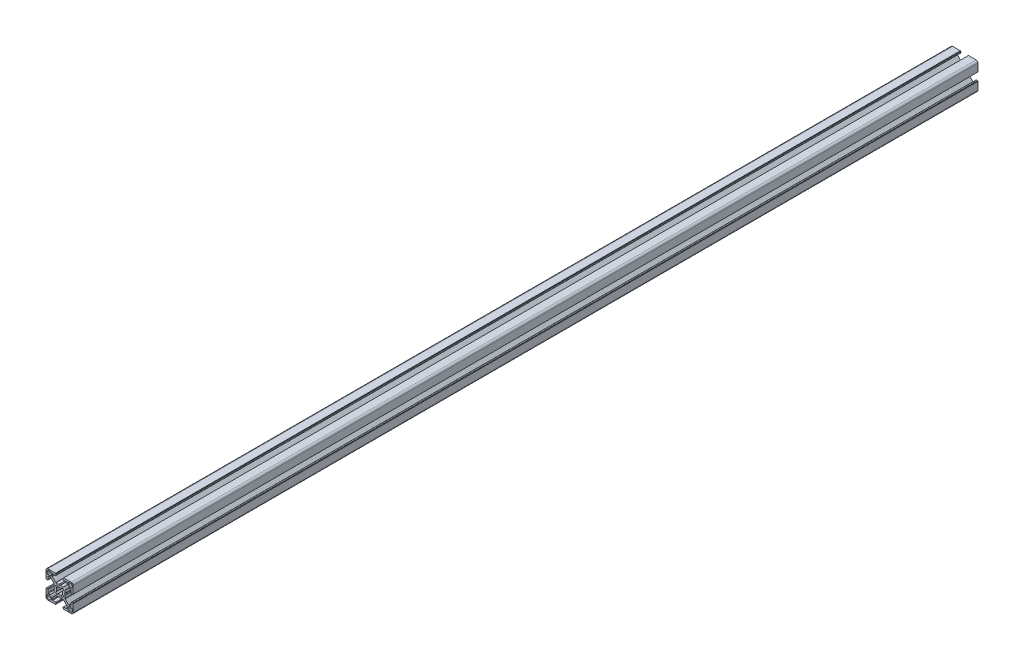
SolidWorks part; units mm, degrees
ref_plane "Front Plane" through (0, 0, 0) normal (0, 0, 1) x (1, 0, 0)
ref_plane "Top Plane" through (0, 0, 0) normal (0, 1, 0) x (1, 0, 0)
ref_plane "Right Plane" through (0, 0, 0) normal (1, 0, 0) x (0, 0, -1)
sketch "Sketch1" plane through (0, 0, 0) normal (0, 0, 1) x (1, 0, 0)
  line L0 (-15, 0) -> (15, 0) construction
  line L1 (0, -15) -> (0, 15) construction
  line L2 (-4.5, 15) -> (4.5, 15) construction
  line L3 (-4, -15) -> (4, -15) construction
  line L4 (-4.5, 15) -> (-4.5, 14.5)
  line L5 (-4.5, 14.5) -> (-4, 14.5)
  line L6 (-4, 14.5) -> (-4, 13.29)
  line L7 (-4.5, 12.79) -> (-7.7675, 12.79)
  line L8 (-8.2675, 12.29) -> (-8.2675, 10.2707)
  line L9 (-8.1211, 9.9171) -> (-4.3504, 6.1464)
  line L10 (-3.9968, 6) -> (0, 6)
  line L11 (0, 0) -> (-15, 15) construction
  line L12 (-4.5, 15) -> (-12.968, 15)
  line L14 (-12.705, 9.5135) -> (-10.5135, 9.5135)
  line L15 (-13.705, 10.5135) -> (-13.705, 12.705)
  line L16 (-12.705, 13.705) -> (-10.5135, 13.705)
  line L17 (-9.5135, 10.5135) -> (-9.5135, 12.705)
  line L18 (-13.705, 9.5135) -> (-9.5135, 13.705) construction
  line L19 (-13.705, 13.705) -> (-9.5135, 9.5135) construction
  line L20 (-3.1568, 4.5038) -> (-1.5303, 3.1477) construction
  line L21 (-4.5038, 3.1568) -> (-3.1477, 1.5303) construction
  line L22 (-6, 3.9968) -> (-6, 0)
  line L23 (-9.9171, 8.1211) -> (-6.1464, 4.3504)
  line L24 (-15, 4.5) -> (-15, 12.968)
  line L25 (-12.29, 8.2675) -> (-10.2707, 8.2675)
  line L26 (-12.79, 4.5) -> (-12.79, 7.7675)
  line L27 (-14.5, 4) -> (-13.29, 4)
  line L28 (-14.5, 4.5) -> (-14.5, 4)
  line L29 (-15, 4.5) -> (-14.5, 4.5)
  circle A0 centre (0, 0) radius 3.5
  arc A1 (-12.968, 15) -> (-15, 12.968) centre (-12.968, 12.968) ccw
  circle A2 centre (0, 0) radius 5.5 construction
  arc A3 (-10.5135, 9.5135) -> (-9.5135, 10.5135) centre (-10.5135, 10.5135) ccw
  arc A4 (-13.705, 12.705) -> (-12.705, 13.705) centre (-12.705, 12.705) cw
  arc A5 (-10.5135, 13.705) -> (-9.5135, 12.705) centre (-10.5135, 12.705) cw
  arc A6 (-12.705, 9.5135) -> (-13.705, 10.5135) centre (-12.705, 10.5135) cw
  arc A7 (-12.79, 4.5) -> (-13.29, 4) centre (-13.29, 4.5) cw
  arc A8 (-12.29, 8.2675) -> (-12.79, 7.7675) centre (-12.29, 7.7675) ccw
  arc A9 (-9.9171, 8.1211) -> (-10.2707, 8.2675) centre (-10.2707, 7.7675) ccw
  arc A10 (-6, 3.9968) -> (-6.1464, 4.3504) centre (-6.5, 3.9968) ccw
  arc A11 (-4.3504, 6.1464) -> (-3.9968, 6) centre (-3.9968, 6.5) ccw
  arc A12 (-4, 13.29) -> (-4.5, 12.79) centre (-4.5, 13.29) cw
  arc A13 (-7.7675, 12.79) -> (-8.2675, 12.29) centre (-7.7675, 12.29) ccw
  arc A14 (-8.2675, 10.2707) -> (-8.1211, 9.9171) centre (-7.7675, 10.2707) ccw
  point P4 (0, 0)
  point P8 (0, 0)
  point P13 (0, 15)
  point P15 (0, -15)
  point P16 (0, 6)
  point P23 (-11.6092, 11.6093)
  point P26 (0, 6)
  point P62 (-12.79, 4)
  point P65 (-12.79, 8.2675)
  point P68 (-10.0636, 8.2675)
  point P71 (-6, 4.2039)
  point P74 (-4.2039, 6)
  point P77 (-4, 12.79)
  point P80 (-8.2675, 12.79)
  point P83 (-8.2675, 10.0636)
  dimension "Center Hole Diameter" = 7
  dimension "D11" = 2.032
  dimension "D9" = 11
  dimension "D13" = 1
  dimension "D14" = 0.5
  dimension "Rail Height" = 30
  dimension "Rail Width" = 30
  dimension "T-Slot Width" = 8
  dimension "T-Slot Depth" = 9
  dimension "D1" = 9
  dimension "D2" = 45
  dimension "D3" = 8
  dimension "D4" = 2.21
  dimension "D5" = 16.535
  dimension "D7" = 2.54
  dimension "D6" = 1.295
  dimension "D8" = 1.246
  dimension "D10" = 10.36
  dimension "D12" = 1.905
sketch "Sketch2" plane through (0, 0, 0) normal (1, 0, 0) x (0, 0, -1)
  line L0 (-76.2, 0) -> (76.2, 0) construction
  line L2 (0, -15) -> (0, 15) construction
  line L3 (0, -15) -> (0, 15) construction
  line L4 (-76.2, -15) -> (-76.2, 15) construction
  line L5 (76.2, -15) -> (76.2, 15) construction
  point P0 (-38.7, 0)
  point P3 (0, 0)
  point P4 (38.7, 0)
  point P12 (-76.2, 0)
  point P14 (76.2, 0)
  dimension "Length" = 152.4
  dimension "D1" = 37.5
sketch "Sketch3" plane through (0, 0, 0) normal (0, 0, 1) x (1, 0, 0)
  line L0 (-4.5038, 3.1568) -> (-3.1477, 1.5303)
  line L1 (0, 3.5) -> (0, 5.5)
  line L2 (-5.5, 0) -> (-3.5, 0)
  line L7 (-6, 3.9968) -> (-6, 0) construction
  line L31 (-9.9171, 8.1211) -> (-6.1464, 4.3504) construction
  line L117 (-12.29, 8.2675) -> (-10.2707, 8.2675) construction
  line L118 (-12.79, 4.5) -> (-12.79, 7.7675) construction
  line L157 (-12.705, 9.5135) -> (-10.5135, 9.5135)
  line L158 (-9.5135, 10.5135) -> (-9.5135, 12.705)
  line L163 (-10.5135, 13.705) -> (-12.705, 13.705)
  line L164 (-13.705, 12.705) -> (-13.705, 10.5135)
  line L165 (-12.705, 9.5135) -> (-10.5135, 9.5135)
  line L166 (-9.5135, 10.5135) -> (-9.5135, 12.705)
  line L167 (-10.5135, 13.705) -> (-12.705, 13.705)
  line L168 (-13.705, 12.705) -> (-13.705, 10.5135)
  line L169 (-14.5, 4) -> (-13.29, 4) construction
  line L170 (-14.5, 4.5) -> (-14.5, 4) construction
  line L171 (-15, 4.5) -> (-14.5, 4.5) construction
  line L172 (-15, 4.5) -> (-15, 12.968) construction
  line L173 (-4.5, 15) -> (-12.968, 15) construction
  line L174 (-4.5, 15) -> (-4.5, 14.5) construction
  line L175 (-4.5, 14.5) -> (-4, 14.5) construction
  line L176 (-4, 14.5) -> (-4, 13.29) construction
  line L177 (-4.5, 12.79) -> (-7.7675, 12.79) construction
  line L178 (-8.2675, 12.29) -> (-8.2675, 10.2707) construction
  line L179 (-8.1211, 9.9171) -> (-4.3504, 6.1464) construction
  line L180 (-3.9968, 6) -> (0, 6) construction
  line L181 (-6, 3.9968) -> (-6, 0.866)
  line L182 (-9.9171, 8.1211) -> (-6.1464, 4.3504)
  line L183 (-12.29, 8.2675) -> (-10.2707, 8.2675)
  line L184 (-12.79, 4.5) -> (-12.79, 7.7675)
  line L185 (-14.5, 4) -> (-13.29, 4)
  line L186 (-14.5, 4.5) -> (-14.5, 4)
  line L187 (-15, 4.5) -> (-14.5, 4.5)
  line L188 (-15, 4.5) -> (-15, 12.968)
  line L189 (-4.5, 15) -> (-12.968, 15)
  line L190 (-4.5, 15) -> (-4.5, 14.5)
  line L191 (-4.5, 14.5) -> (-4, 14.5)
  line L192 (-4, 14.5) -> (-4, 13.29)
  line L193 (-4.5, 12.79) -> (-7.7675, 12.79)
  line L194 (-8.2675, 12.29) -> (-8.2675, 10.2707)
  line L195 (-8.1211, 9.9171) -> (-4.3504, 6.1464)
  line L196 (-3.9968, 6) -> (-0.866, 6)
  line L197 (-0.866, 6) -> (0, 5.5)
  line L198 (0, -15) -> (0, 15) construction
  line L199 (0, 0) -> (-15, 15) construction
  line L200 (0, 0) -> (-15, 15) construction
  line L201 (-3.1568, 4.5038) -> (-1.5303, 3.1477) construction
  line L202 (-3.1568, 4.5038) -> (-1.5303, 3.1477)
  line L203 (-6, 0.866) -> (-5.5, 0)
  line L204 (-15, 0) -> (15, 0) construction
  line L205 (-15, 0) -> (15, 0) construction
  line L206 (0, -15) -> (0, 15) construction
  arc A0 (-3.5, 0) -> (-3.1477, 1.5303) centre (0, 0) cw
  arc A10 (-6, 3.9968) -> (-6.1464, 4.3504) centre (-6.5, 3.9968) ccw construction
  circle A16 centre (0, 0) radius 3.5
  arc A18 (0, 3.5) -> (-1.5303, 3.1477) centre (0, 0) ccw
  arc A20 (-9.9171, 8.1211) -> (-10.2707, 8.2675) centre (-10.2707, 7.7675) ccw construction
  arc A22 (-12.29, 8.2675) -> (-12.79, 7.7675) centre (-12.29, 7.7675) ccw construction
  arc A28 (-13.29, 4) -> (-12.79, 4.5) centre (-13.29, 4.5) ccw construction
  arc A29 (-10.5135, 9.5135) -> (-9.5135, 10.5135) centre (-10.5135, 10.5135) ccw
  arc A30 (-9.5135, 12.705) -> (-10.5135, 13.705) centre (-10.5135, 12.705) ccw
  arc A31 (-12.705, 13.705) -> (-13.705, 12.705) centre (-12.705, 12.705) ccw
  arc A32 (-13.705, 10.5135) -> (-12.705, 9.5135) centre (-12.705, 10.5135) ccw
  arc A33 (-10.5135, 9.5135) -> (-9.5135, 10.5135) centre (-10.5135, 10.5135) ccw
  arc A34 (-9.5135, 12.705) -> (-10.5135, 13.705) centre (-10.5135, 12.705) ccw
  arc A35 (-12.705, 13.705) -> (-13.705, 12.705) centre (-12.705, 12.705) ccw
  arc A36 (-13.705, 10.5135) -> (-12.705, 9.5135) centre (-12.705, 10.5135) ccw
  arc A37 (-12.968, 15) -> (-15, 12.968) centre (-12.968, 12.968) ccw construction
  arc A38 (-4.5, 12.79) -> (-4, 13.29) centre (-4.5, 13.29) ccw construction
  arc A39 (-7.7675, 12.79) -> (-8.2675, 12.29) centre (-7.7675, 12.29) ccw construction
  arc A40 (-8.2675, 10.2707) -> (-8.1211, 9.9171) centre (-7.7675, 10.2707) ccw construction
  arc A41 (-4.3504, 6.1464) -> (-3.9968, 6) centre (-3.9968, 6.5) ccw construction
  arc A42 (-6, 3.9968) -> (-6.1464, 4.3504) centre (-6.5, 3.9968) ccw
  arc A43 (-9.9171, 8.1211) -> (-10.2707, 8.2675) centre (-10.2707, 7.7675) ccw
  arc A44 (-12.29, 8.2675) -> (-12.79, 7.7675) centre (-12.29, 7.7675) ccw
  arc A45 (-13.29, 4) -> (-12.79, 4.5) centre (-13.29, 4.5) ccw
  arc A46 (-12.968, 15) -> (-15, 12.968) centre (-12.968, 12.968) ccw
  arc A47 (-4.5, 12.79) -> (-4, 13.29) centre (-4.5, 13.29) ccw
  arc A48 (-7.7675, 12.79) -> (-8.2675, 12.29) centre (-7.7675, 12.29) ccw
  arc A49 (-8.2675, 10.2707) -> (-8.1211, 9.9171) centre (-7.7675, 10.2707) ccw
  arc A50 (-4.3504, 6.1464) -> (-3.9968, 6) centre (-3.9968, 6.5) ccw
  circle A51 centre (0, 0) radius 5.5 construction
  arc A52 (-3.1568, 4.5038) -> (-4.5038, 3.1568) centre (0, 0) ccw
  dimension "D3" = 60
  dimension "D4" = 60
  dimension "D1" = 0
  dimension "D2" = 0
extrude "Boss-Extrude1" add sketch "Sketch3" along normal mid plane 1000
pattern_circular "CirPattern1" count 4 over 360 about axis through (0, 0, 76.2) along (0, 0, -1) of "Boss-Extrude1"
ref_plane "Contact Plane1" through (15, 0, 0) normal (1, 0, 0) x (0, 0, -1)
ref_plane "Contact Plane2" through (0, -15, 0) normal (0, 1, 0) x (1, 0, 0)
ref_plane "Contact Plane3" through (-15, 0, 0) normal (1, 0, 0) x (0, 0, -1)
ref_plane "Contact Plane4" through (0, 15, 0) normal (0, 1, 0) x (1, 0, 0)
equation "\"D1@Sketch2\" = \"Rail Height@Sketch1\" * 1.25"
equation "\"D1@Sketch1\"=\"T-Slot Width@Sketch1\"+1mm"
equation "\"D3@Sketch1\"=\"T-Slot Width@Sketch1\""
equation "\"D1@Boss-Extrude1\"=\"length\""
equation "\"length\" = 1000"
